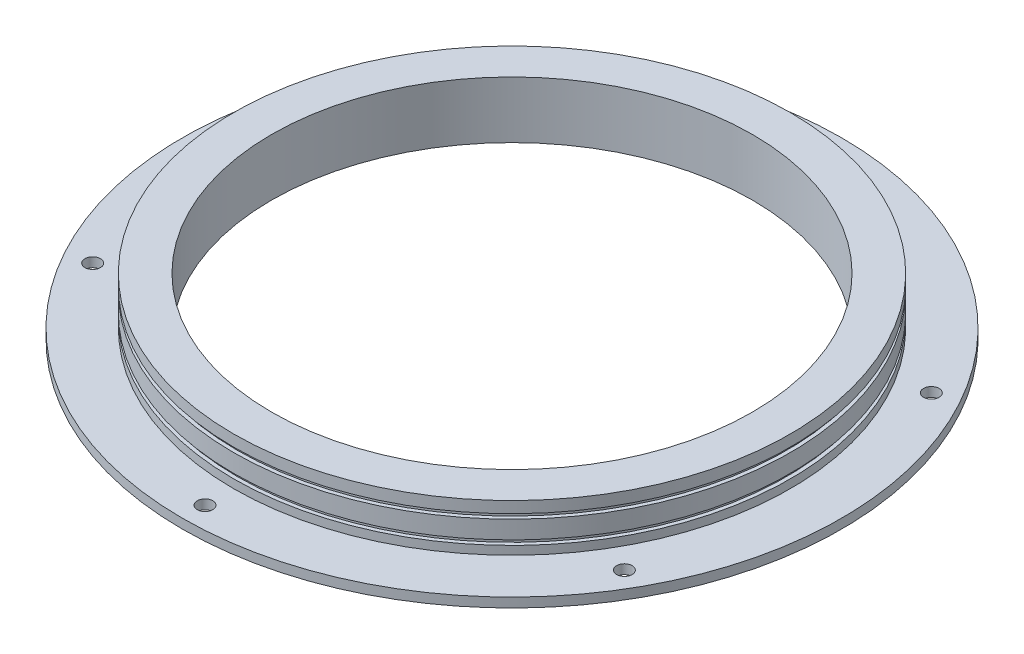
SolidWorks part; units mm, degrees
ref_plane "Front Plane" through (0, 0, 0) normal (0, 0, 1) x (1, 0, 0)
ref_plane "Top Plane" through (0, 0, 0) normal (0, 1, 0) x (1, 0, 0)
ref_plane "Right Plane" through (0, 0, 0) normal (1, 0, 0) x (0, 0, -1)
sketch "Sketch1" plane through (0, 0, 0) normal (0, 1, 0) x (1, 0, 0)
  line L0 (0, 150) -> (0, 173.85) construction
  circle A0 centre (0, 0) radius 146.85
  circle A1 centre (0, 0) radius 173.85
  circle A2 centre (0, 0) radius 126.85
  circle A3 centre (0, 0) radius 144.85
  circle A4 centre (0, 161.925) radius 4.1
  circle A5 centre (140.2312, 80.9625) radius 4.1
  circle A6 centre (140.2312, -80.9625) radius 4.1
  circle A7 centre (0, -161.925) radius 4.1
  circle A8 centre (-140.2312, -80.9625) radius 4.1
  circle A9 centre (-140.2312, 80.9625) radius 4.1
  circle A10 centre (0, 0) radius 150 construction
  point P23 (0, 0)
  dimension "D1" = 293.7
  dimension "D5" = 8.2
  dimension "D7" = 300
  dimension "D2" = 27
  dimension "D3" = 20
  dimension "D4" = 2
  dimension "D6" = 6
extrude "Boss-Extrude1" add sketch "Sketch1" along normal blind 5 contours A3 A2 | A0 A3 | A1 A4 A0 region at (-146.4346, 0, 0) region at (-168.9328, 0, 0) region at (-140.753, 0, 0)
extrude "Boss-Extrude2" add sketch "Sketch1<3>" along normal blind 30 contours A3 A2 | A0 A3 region at (-146.4346, 0, 0) region at (-140.753, 0, 0)
sketch "Sketch1<3>" plane through (0, 0, 0) normal (0, 1, 0) x (1, 0, 0) same geometry as "Sketch1"
extrude "Cut-Extrude1" cut sketch "Sketch1<4>" against normal blind 2.5 from offset 12 contours A0 A3 region at (-146.4346, 0, 0)
sketch "Sketch1<4>" plane through (0, 0, 0) normal (0, 1, 0) x (1, 0, 0) same geometry as "Sketch1"
extrude "Cut-Extrude2" cut sketch "Sketch1<5>" against normal blind 2.5 from offset 24 contours A0 A3 region at (-146.4346, 0, 0)
sketch "Sketch1<5>" plane through (0, 0, 0) normal (0, 1, 0) x (1, 0, 0) same geometry as "Sketch1"
equation "\"acTubeOD\"= 300mm"
equation "\"acTubeThickness\"= 3mm"
equation "\"acTubeLength\"= 300mm"
equation "\"threadedRodDiam\"= 8mm"
equation "\"D1@Sketch1\"=\"acTubeOD\"-\"acTubeThickness\"*2-0.3"
equation "\"D2@Sketch1\" = \"acTubeThickness\" + \"flange width\""
equation "\"D5@Sketch1\" = \"threadedRodDiam\" + 0.2"
equation "\"D7@Sketch1\"=\"acTubeOD\""
equation "\"flange width\"= 24mm"
